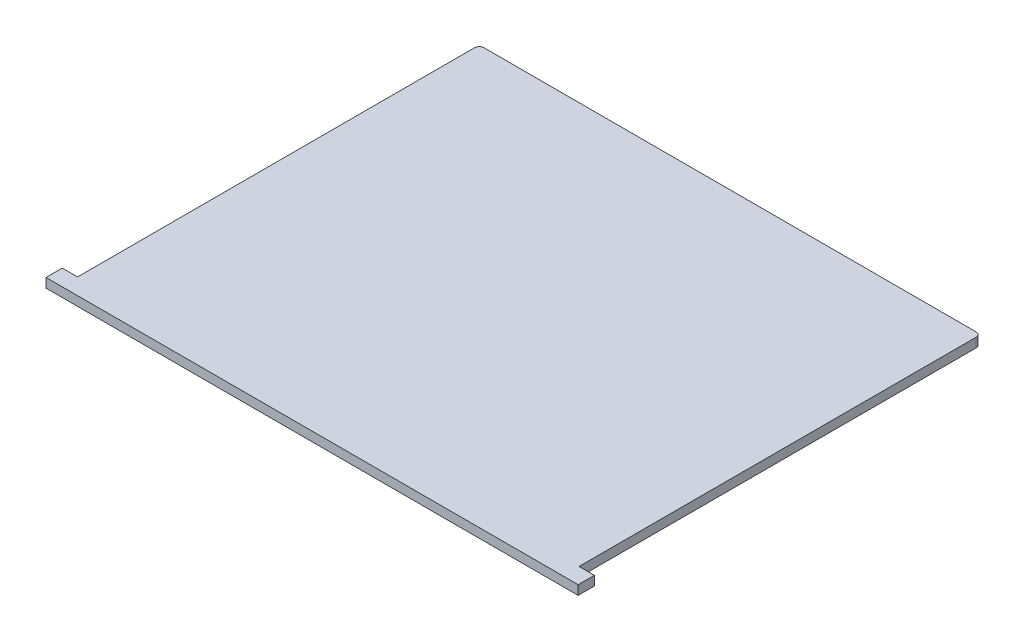
SolidWorks part; units mm, degrees
material "ABS"
ref_plane "Front Plane" through (0, 0, 0) normal (0, 0, 1) x (1, 0, 0)
ref_plane "Top Plane" through (0, 0, 0) normal (0, 1, 0) x (1, 0, 0)
ref_plane "Right Plane" through (0, 0, 0) normal (1, 0, 0) x (0, 0, -1)
sketch "Sketch1" plane through (0, 0, 0) normal (0, 1, 0) x (1, 0, 0)
  line L1 (-27, -22.5) -> (27, -22.5)
  line L3 (-27, 22.5) -> (27, 22.5)
  line L5 (-27, -22.5) -> (27, 22.5) construction
  line L6 (-27, 22.5) -> (27, -22.5) construction
  line L17 (-27, 22.5) -> (-27, -20.75)
  line L18 (-28.65, -20.75) -> (-28.65, -22.5)
  line L19 (-28.65, -22.5) -> (-27, -22.5)
  line L20 (-27, -20.75) -> (-28.65, -20.75)
  line L21 (27, 22.5) -> (27, -20.75)
  line L22 (27, -20.75) -> (28.65, -20.75)
  line L23 (28.65, -20.75) -> (28.65, -22.5)
  line L24 (28.65, -22.5) -> (27, -22.5)
  point P0 (0, 0)
  dimension "D1" = 1.75
  dimension "D2" = 1.65
  dimension "D3" = 54
  dimension "D4" = 45
  dimension "D5" = 1.65
  dimension "D6" = 1.75
extrude "Boss-Extrude1" add sketch "Sketch1" along normal blind 1
fillet "Fillet1" radius 0.5 2 edges at (27, 0.5, -22.5) (-27, 0.5, -22.5)
